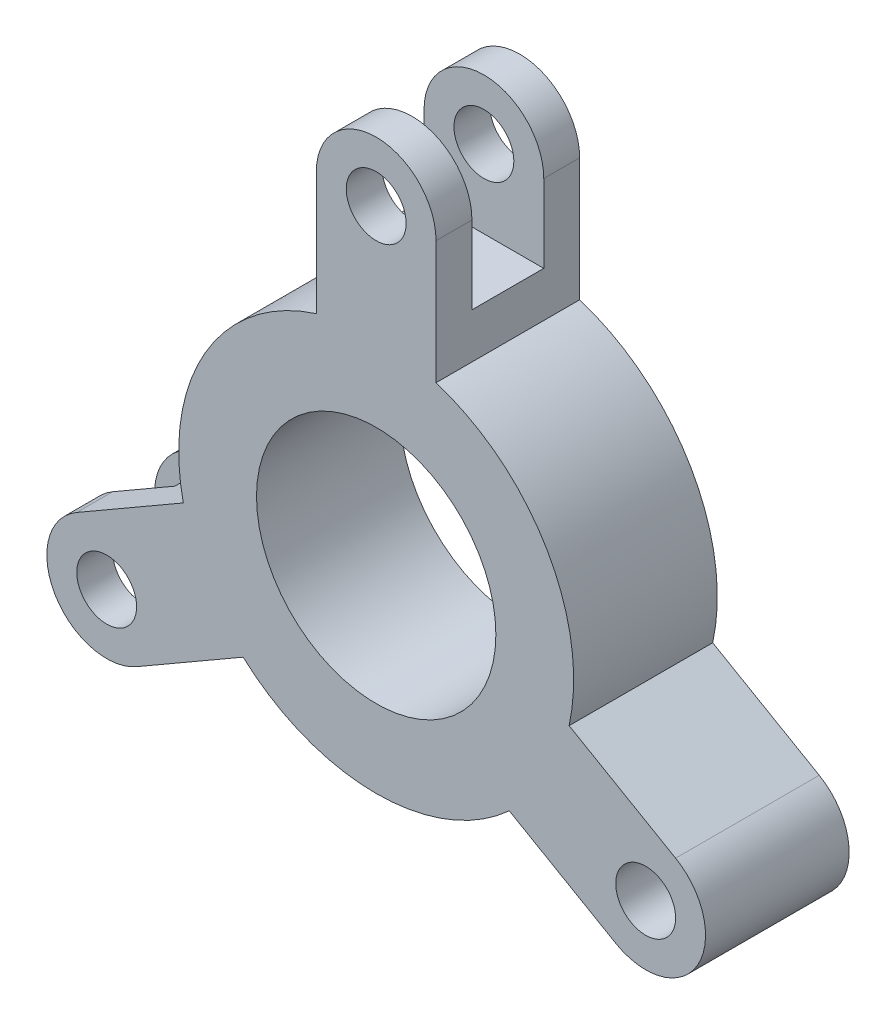
SolidWorks part; units mm, degrees
ref_plane "Спереди" through (0, 0, 0) normal (0, 0, 1) x (1, 0, 0)
ref_plane "Сверху" through (0, 0, 0) normal (0, 1, 0) x (1, 0, 0)
ref_plane "Справа" through (0, 0, 0) normal (1, 0, 0) x (0, 0, -1)
sketch "Эскиз1" plane through (0, 0, 0) normal (0, 0, 1) x (1, 0, 0)
  line L0 (0, 0) -> (0, 26) construction
  line L1 (-5, 0) -> (-5, 26)
  line L2 (5, 0) -> (5, 26)
  line L3 (0, 0) -> (22.5167, -13) construction
  line L4 (2.5, 4.3301) -> (25.0167, -8.6699)
  line L5 (-2.5, -4.3301) -> (20.0167, -17.3301)
  line L6 (0, 0) -> (-22.5167, -13) construction
  line L7 (2.5, -4.3301) -> (-20.0167, -17.3301)
  line L8 (-2.5, 4.3301) -> (-25.0167, -8.6699)
  circle A0 centre (0, 0) radius 10
  circle A1 centre (0, 0) radius 16.5
  arc A2 (-5, 0) -> (5, 0) centre (0, 0) ccw
  arc A3 (5, 26) -> (-5, 26) centre (0, 26) ccw
  circle A4 centre (0, 26) radius 2.5
  circle A5 centre (22.5167, -13) radius 2.5
  arc A6 (2.5, 4.3301) -> (-2.5, -4.3301) centre (0, 0) ccw
  arc A7 (20.0167, -17.3301) -> (25.0167, -8.6699) centre (22.5167, -13) ccw
  circle A8 centre (-22.5167, -13) radius 2.5
  arc A9 (2.5, -4.3301) -> (-2.5, 4.3301) centre (0, 0) ccw
  arc A10 (-25.0167, -8.6699) -> (-20.0167, -17.3301) centre (-22.5167, -13) ccw
  point P5 (0, 13)
  point P16 (11.2583, -6.5)
  point P24 (-11.2583, -6.5)
  point P31 (0, 0)
  dimension "D1" = 20
  dimension "D2" = 33
  dimension "D4" = 5
  dimension "D3" = 26
  dimension "D5" = 10
  dimension "D6" = 3
extrude "Бобышка-Вытянуть1" add sketch "Эскиз1" along normal blind 6 and the other way blind 6 contours L4 A1 L2 A0 | L2 A1 L1 A0 | L1 A1 L8 A0 | L8 A1 L7 A0 | L7 A1 L5 A0 | L5 A1 L4 A0 | L5 A7 L4 A1 A5 | L8 A10 L7 A1 A8 | L2 A3 L1 A1 A4 region at (-10.97, 6.3335, 0) region at (0, 12.8973, 0) region at (-11.1694, -6.4486, 0) region at (0, 22.648, 0) region at (10.97, 6.3335, 0) region at (-19.6137, -11.324, 0) region at (0, -12.667, 0) region at (11.1694, -6.4486, 0) region at (19.6137, -11.324, 0)
sketch "Эскиз2" plane through (0, 0, 0) normal (0, 0, 1) x (1, 0, 0)
  line L1 (-7.5, 19.5) -> (7.5, 19.5)
  line L2 (-7.5, 19.5) -> (-7.5, 32.5)
  line L3 (-7.5, 32.5) -> (7.5, 32.5)
  line L4 (7.5, 19.5) -> (7.5, 32.5)
  line L5 (-7.5, 19.5) -> (7.5, 32.5) construction
  line L6 (-7.5, 32.5) -> (7.5, 19.5) construction
  point P0 (0, 26)
  dimension "D1" = 13
  dimension "D2" = 15
extrude "Вырез-Вытянуть1" cut sketch "Эскиз2" against normal blind 3 and the other way blind 3
sketch "Эскиз3" plane through (0, 0, -3) normal (0, 0, 1) x (1, 0, 0)
  line L0 (-22.2128, -25.5263) -> (-11.8205, -19.5263)
  line L1 (-22.2128, -25.5263) -> (-33.2128, -6.4737)
  line L2 (-11.8205, -19.5263) -> (-22.8205, -0.4737)
  line L3 (-33.2128, -6.4737) -> (-22.8205, -0.4737)
  line L4 (-22.2128, -25.5263) -> (-22.8205, -0.4737) construction
  line L5 (-11.8205, -19.5263) -> (-33.2128, -6.4737) construction
  line L6 (-22.5167, -13) -> (0, 0) construction
  point P1 (-22.5167, -13)
  dimension "D1" = 12
  dimension "D2" = 22
extrude "Вырез-Вытянуть2" cut sketch "Эскиз3" along normal up to surface (6 mm away) up to face at (-2.5, 26, 3)
